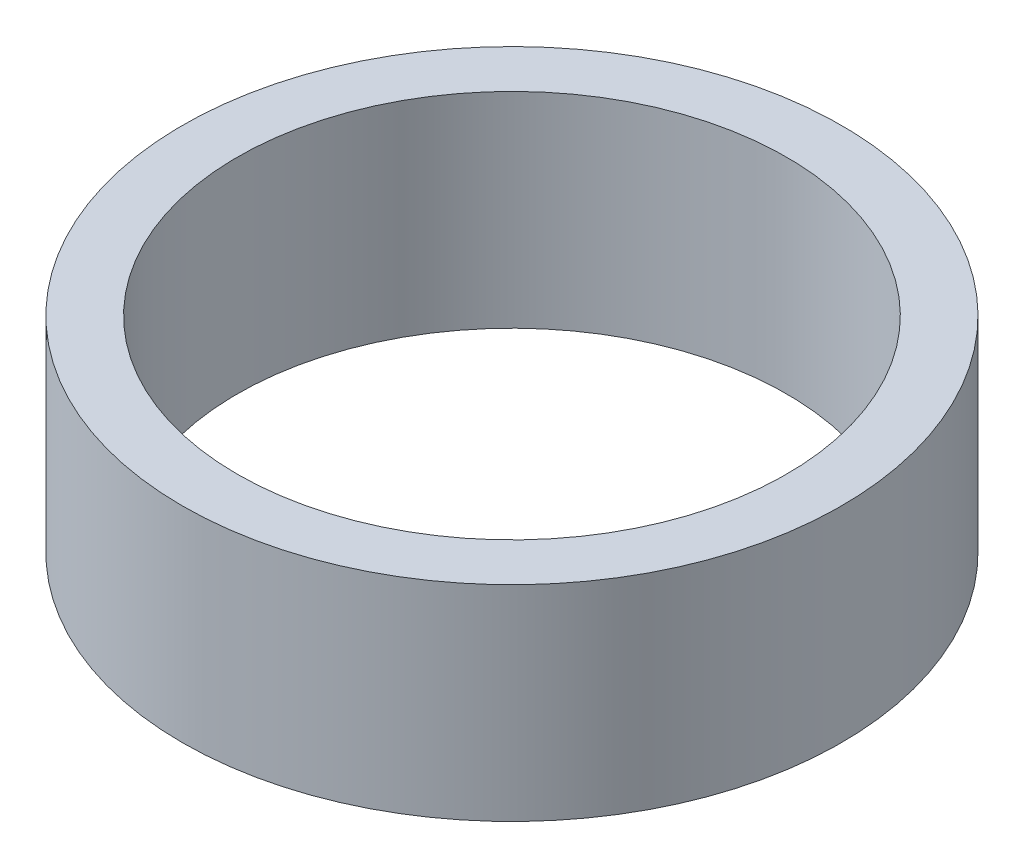
SolidWorks part; units mm, degrees
ref_plane "Front Plane" through (0, 0, 0) normal (0, 0, 1) x (1, 0, 0)
ref_plane "Top Plane" through (0, 0, 0) normal (0, 1, 0) x (1, 0, 0)
ref_plane "Right Plane" through (0, 0, 0) normal (1, 0, 0) x (0, 0, -1)
sketch "Sketch1" plane through (0, 0, 0) normal (0, 1, 0) x (1, 0, 0)
  circle A0 centre (0, 0) radius 45
  dimension "FLANGE_OD" = 90
extrude "Boss-Extrude1" add sketch "Sketch1" along normal blind 28
sketch "Sketch2" plane through (0, 0, 0) normal (0, 1, 0) x (1, 0, 0)
  circle A0 centre (0, 0) radius 37.5
  dimension "BORE_D" = 75
extrude "Cut-Extrude1" cut sketch "Sketch2" along normal through all
sketch "Sketch3" plane through (0, 28, 0) normal (0, 1, 0) x (1, 0, 0)
  circle A0 centre (0, 0) radius 20.8302 construction
  circle A1 centre (-20.8302, 0) radius 1.5
  dimension "BOLT_D" = 3
  dimension "BOLT_PCD" = 41.6604
extrude "Cut-Extrude2" cut sketch "Sketch3" against normal blind 24.1657 rebuild error yes
pattern_circular "CirPattern1" count 4 over 360 rebuild error yes
